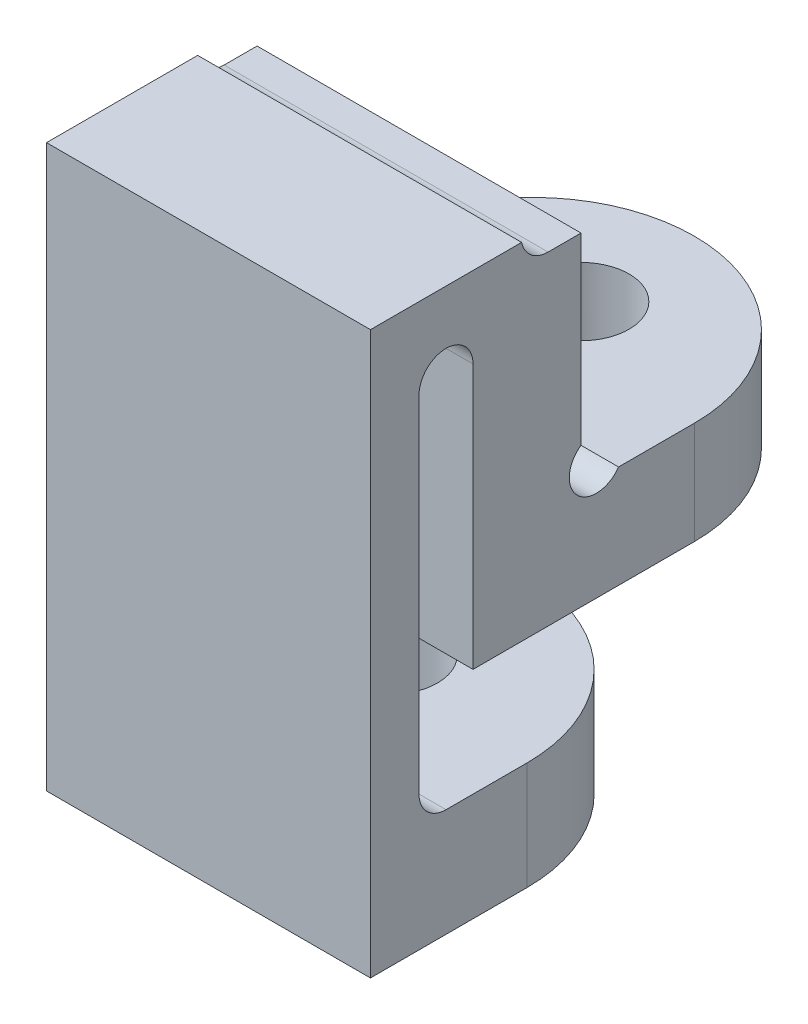
SolidWorks part; units mm, degrees
material "Copper"
ref_plane "Front Plane" through (0, 0, 0) normal (0, 0, 1) x (1, 0, 0)
ref_plane "Top Plane" through (0, 0, 0) normal (0, 1, 0) x (1, 0, 0)
ref_plane "Right Plane" through (0, 0, 0) normal (1, 0, 0) x (0, 0, -1)
ref_plane "Plane1" through (7.5, 0, 0) normal (1, 0, 0) x (0, 0, -1)
sketch "Sketch1" plane through (7.5, 0, 0) normal (1, 0, 0) x (0, 0, -1)
  line L3 (-2, 0.4976) -> (-2, 5.3976)
  line L4 (-1, 0.4976) -> (-1, 5.3976)
  line L5 (6.1, 0.4976) -> (-1, 0.4976)
  line L6 (6.1, 6.8976) -> (6.1, 0.4976)
  line L7 (-1.5, 5.8976) -> (-1.5, 20.4976) construction
  line L9 (6.1, 6.8976) -> (-2.9, 6.8976)
  line L11 (-2, 0.4976) -> (-2, -1.5024)
  line L12 (-2, -1.5024) -> (3, -1.5024)
  line L13 (3, -1.5024) -> (3, -3.5024)
  line L14 (3, -3.5024) -> (-2.9, -3.5024)
  line L15 (-2.9, 6.8976) -> (-2.9, -3.5024)
  arc A0 (-2, 5.3976) -> (-1, 5.3976) centre (-1.5, 5.3976) cw
  dimension "D1" = 2
  dimension "D2" = 1
  dimension "D3" = 1
  dimension "D5" = 2
  dimension "D6" = 6.4
  dimension "D7" = 5
  dimension "D8" = 0.9
  dimension "D9" = 9
extrude "Boss-Extrude1" add sketch "Sketch1" against normal blind 6
sketch "Sketch2" plane through (1.5, 0, 0) normal (-1, 0, 0) x (0, 0, 1)
  line L0 (0, 15.5) -> (0.001, 15.5)
  line L1 (0.001, 15.5) -> (0.001, 20.5)
  line L2 (0.001, 20.5) -> (0, 20.5)
  line L3 (0, 20.5) -> (0, 15.5)
extrude "Cut-Extrude1" [suppressed] cut sketch "Sketch2" against normal blind 7.5
sketch3d "3DSketch1" plane through (0, 0, 0) normal (0, 0, 1) x (1, 0, 0)
  dimension "D1" = 0.5
sketch "Sketch3" plane through (1.5, 0, 0) normal (-1, 0, 0) x (0, 0, 1)
  line L0 (3, 22.4976) -> (3, 6.4976)
  line L1 (3, 6.4976) -> (10.6, 6.4976)
  line L2 (10.6, 6.4976) -> (10.6, 22.4976)
  line L3 (10.6, 22.4976) -> (3, 22.4976)
  line L4 (1.55, 20.4976) -> (1.55, 19.5006) construction
  line L5 (1, 5.3976) -> (1, 0.4976) construction
  line L6 (-7.5, 22.4976) -> (0.1, 22.4976)
  line L7 (-7.5, 6.4976) -> (-7.5, 22.4976)
  line L8 (0.1, 6.4976) -> (-7.5, 6.4976)
  line L9 (0.1, 22.4976) -> (0.1, 6.4976)
  dimension "D1" = 16
  dimension "D2" = 0.9
extrude "Cut-Extrude2" cut sketch "Sketch3" against normal through all
sketch "Sketch4" plane through (1.5, 0, 0) normal (-1, 0, 0) x (0, 0, 1)
  line L1 (-1.7071, 2.3976) -> (-1, 2.3976)
  line L4 (1.5, 20.4976) -> (1.5, 5.8976) construction
  line L5 (-1, 2.3976) -> (-1, 3.2047)
  line L6 (-7.5, 6.4976) -> (-1, 6.4976)
  line L7 (-7.5, 2.3976) -> (-7.5, 6.4976)
  line L8 (-1.7071, 2.3976) -> (-7.5, 2.3976)
  line L10 (-6.1, 6.4976) -> (0.1, 6.4976) construction
  line L13 (-1, 3.2047) -> (-1, 6.4976)
  arc A0 (2, 5.3976) -> (1, 5.3976) centre (1.5, 5.3976) ccw construction
  dimension "D1" = 4.1
  dimension "D2" = 0
  dimension "D5" = 6.5
extrude "Cut-Extrude3" cut sketch "Sketch4" against normal through all
sketch "Sketch5" plane through (1.5, 0, 0) normal (-1, 0, 0) x (0, 0, 1)
  line L0 (1, 4.5) -> (0.999, 4.5)
  line L1 (0.999, 4.5) -> (0.999, 0.5)
  line L2 (0.999, 0.5) -> (1, 0.5)
  line L3 (1, 0.5) -> (1, 4.5)
extrude "Cut-Extrude4" [suppressed] cut sketch "Sketch5" against normal blind 7.5
sketch "Sketch6" plane through (1.5, 0, 0) normal (-1, 0, 0) x (0, 0, 1)
  line L0 (0, 0.5) -> (0.001, 0.5)
  line L1 (0.001, 0.5) -> (0.001, 4.5)
  line L2 (0.001, 4.5) -> (0, 4.5)
  line L3 (0, 4.5) -> (0, 0.5)
extrude "Cut-Extrude5" [suppressed] cut sketch "Sketch6" against normal blind 7.5
hole_wizard "#30 (0.1285) Diameter Hole1" [suppressed] positions "Sketch8" profile "Sketch7" hole size "#30" standard "ANSI Inch"
sketch "Sketch8" [suppressed] plane through (0, 0, 0.001) normal (0, 0, -1) x (-1, 0, 0)
  point P0 (-3.75, 2.5)
sketch "Sketch7" plane through (3.75, 2.5, 0.001) normal (1, 0, 0) x (0, 1, 0)
  line L0 (0, 0) -> (0, 10.499)
  line L1 (0, 10.499) -> (1.6319, 10.499)
  line L2 (1.6319, 10.499) -> (1.6319, 0)
  line L5 (1.6319, 0) -> (0, 0)
  line L11 (0, -6.35) -> (0, 107.95) construction
  dimension "Thru Hole Dia." = 3.2639
  dimension "Thru Hole Depth" = 10.499
fillet "Fillet1" [suppressed] radius 0.5
fillet "Fillet2" radius 3 4 edges at (7.5, 1.4476, -6.1) (1.5, 1.4476, -6.1) (7.5, -2.5024, -3) (1.5, -2.5024, -3) tangent propagation no
fillet "Fillet3" radius 0.5 2 edges at (4.5, 6.4976, 0.1) (4.5, -1.5024, 2)
hole_wizard "#2-56 Tapped Hole1" positions "Sketch9" profile "Sketch10" tap size "#2-56" standard "ANSI Inch"
sketch "Sketch9" plane through (0, 2.3976, 0) normal (0, 1, 0) x (1, 0, 0)
  line L0 (4.5, 2.3839) -> (4.5, 11.5596) construction
  line L2 (7.5, 1) -> (1.5, 1) construction
  point P0 (4.5, 4)
  dimension "D1" = 3
sketch "Sketch10" plane through (4.5, 2.3976, -4) normal (1, 0, 0) x (0, 0, 1)
  line L0 (0, 0) -> (0, 3.5342)
  line L1 (0, 3.5342) -> (0.889, 3)
  line L2 (0.889, 3) -> (0.889, 0)
  line L5 (0.889, 0) -> (0, 0)
  line L10 (0, 3.5342) -> (-0.889, 3) construction
  line L11 (0, -6.35) -> (0, 107.95) construction
  dimension "Tap Drill Dia." = 1.778
  dimension "Tap Drill Depth" = 3
  dimension "Drill Angle" = 118
hole_wizard "#2-56 Tapped Hole2" positions "Sketch11" profile "Sketch12" tap size "#2-56" standard "ANSI Inch"
sketch "Sketch11" plane through (0, -1.5024, 0) normal (0, 1, 0) x (1, 0, 0)
  line L0 (4.5, -1.5) -> (4.5, 7.8361) construction
  line L1 (1.5, -1.5) -> (7.5, -1.5) construction
  point P0 (4.5, 0.45)
  dimension "D1" = 1.95
sketch "Sketch12" plane through (4.5, -1.5024, -0.45) normal (1, 0, 0) x (0, 0, 1)
  line L0 (0, 0) -> (0, 5.8742)
  line L1 (0, 5.8742) -> (0.889, 5.34)
  line L2 (0.889, 5.34) -> (0.889, 0)
  line L5 (0.889, 0) -> (0, 0)
  line L10 (0, 5.8742) -> (-0.889, 5.34) construction
  line L11 (0, -6.35) -> (0, 107.95) construction
  dimension "Tap Drill Dia." = 1.778
  dimension "Tap Drill Depth" = 5.34
  dimension "Drill Angle" = 118
sketch "Sketch13" plane through (1.5, 0, 0) normal (-1, 0, 0) x (0, 0, 1)
  line L0 (-1, 2.3976) -> (-3.7489, 5.1464) construction
  line L1 (-3.1, 2.3976) -> (-1, 2.3976) construction
  circle A1 centre (-1.2828, 2.6804) radius 0.5
  dimension "D1" = 45
  dimension "D2" = 0.4
extrude "Cut-Extrude10" cut sketch "Sketch13" against normal blind 10
